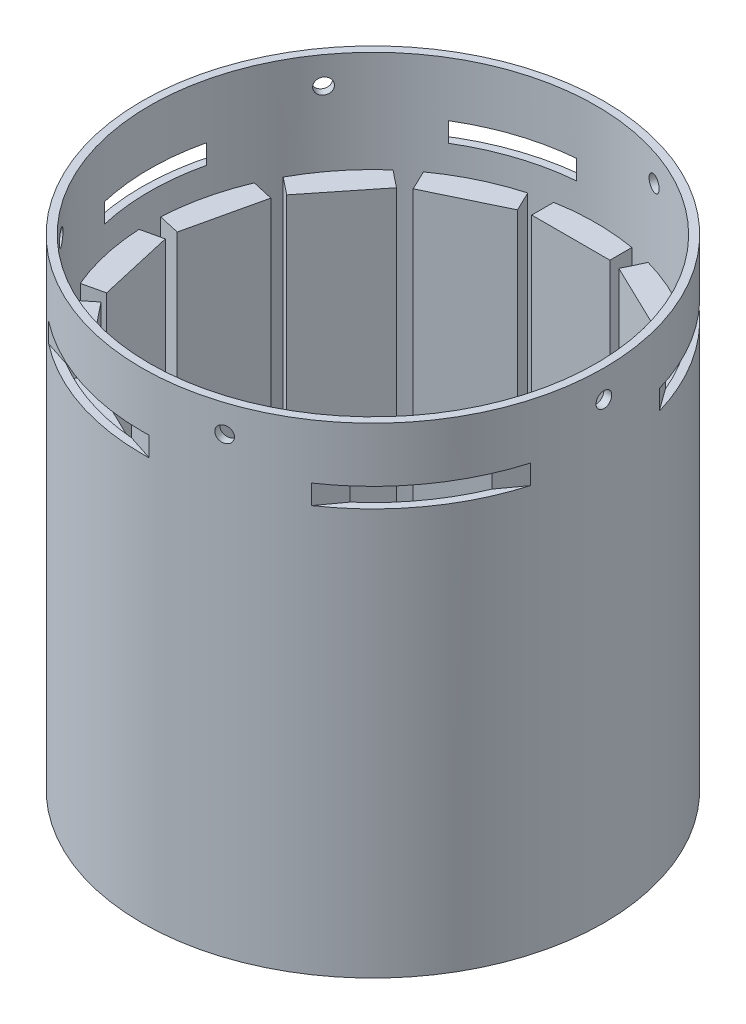
SolidWorks part; units mm, degrees
ref_plane "Front Plane" through (0, 0, 0) normal (0, 0, 1) x (1, 0, 0)
ref_plane "Top Plane" through (0, 0, 0) normal (0, 1, 0) x (1, 0, 0)
ref_plane "Right Plane" through (0, 0, 0) normal (1, 0, 0) x (0, 0, -1)
sketch "Sketch1" plane through (0, 0, 0) normal (0, 1, 0) x (1, 0, 0)
  circle A0 centre (0, 0) radius 29.575
  circle A1 centre (0, 0) radius 28.575
  dimension "D1" = 59.15
  dimension "D2" = 1
extrude "Boss-Extrude1" add sketch "Sketch1" along normal blind 61.5
ref_plane "Plane1" through (0, 4.5, 0) normal (0, -1, 0) x (-1, 0, 0)
sketch "Sketch2" plane through (0, 4.5, 0) normal (0, -1, 0) x (-1, 0, 0)
  line L0 (0, 0) -> (0, 32.3622) construction
  line L1 (-5, 25.325) -> (-5, 28.575)
  line L2 (-5, 25.325) -> (5, 25.325)
  line L3 (-5, 28.575) -> (5, 28.575)
  line L4 (5, 25.325) -> (5, 28.575)
  line L5 (-5, 25.325) -> (5, 28.575) construction
  line L6 (-5, 28.575) -> (5, 25.325) construction
  circle A0 centre (0, 0) radius 28.575 construction
  circle A1 centre (0, 0) radius 28.575
  point P4 (0, 28.575)
  point P6 (0, 26.95)
  dimension "D1" = 3.25
  dimension "D2" = 0
  dimension "D3" = 10
  dimension "D4" = 5
extrude "Boss-Extrude2" add sketch "Sketch2" against normal blind 44 and the other way blind 2.5 contours A1 L1 L2 L4 | A1 L4 L3 region at (0, 4.5, -26.8795) region at (-3.7519, 4.5, -28.4429)
sketch "Sketch3" plane through (0, 0, 0) normal (0, 0, 1) x (1, 0, 0)
  line L0 (0, 0) -> (0, 57.7625) construction
pattern_circular "CirPattern1" count 14 over 360 about axis through (0, 0, 0) along (0, 1, 0) of "Boss-Extrude2" reverse direction yes
ref_plane "Plane2" through (0, 0, 29.575) normal (0, 0, 1) x (1, 0, 0)
sketch "Sketch4" plane through (0, 0, 29.575) normal (0, 0, 1) x (1, 0, 0)
  line L0 (-29.575, 0) -> (29.575, 0) construction
  line L1 (-29.575, 0) -> (29.575, 0)
  line L2 (-29.575, 0) -> (-29.575, 60.8021) construction
  line L3 (28.575, 61.5) -> (-28.575, 61.5) construction
  line L4 (-29.575, 54.5) -> (-27.825, 54.5)
  line L5 (-29.575, 54.5) -> (-29.575, 52)
  line L6 (-29.575, 52) -> (-27.825, 52)
  line L7 (-27.825, 54.5) -> (-27.825, 52)
  dimension "D1" = 7
  dimension "D2" = 2.5
  dimension "D3" = 1.75
extrude "Cut-Extrude1" cut sketch "Sketch4" against normal through all contours L7 L4 L5 L6 region at (-28.7, 53.25, 29.575)
pattern_circular "CirPattern2" count 5 over 360 about axis through (0, 0, 0) along (0, 1, 0) of "Cut-Extrude1"
ref_plane "Plane3" through (8.7767, 0, 27.0119) normal (-0.309, 0, -0.9511) x (-0.9511, 0, 0.309)
sketch "Sketch5" plane through (8.7767, 0, 27.0119) normal (-0.309, 0, -0.9511) x (-0.9511, 0, 0.309)
  line L0 (29.575, 61.5) -> (-29.575, 61.5) construction
  circle A0 centre (0, 58) radius 1
  dimension "D1" = 3.5
extrude "Cut-Extrude2" cut sketch "Sketch5" against normal blind 5 and the other way blind 5
pattern_circular "CirPattern3" count 5 over 360 about axis through (0, 0, 0) along (0, 1, 0) of "Cut-Extrude2" reverse direction yes
